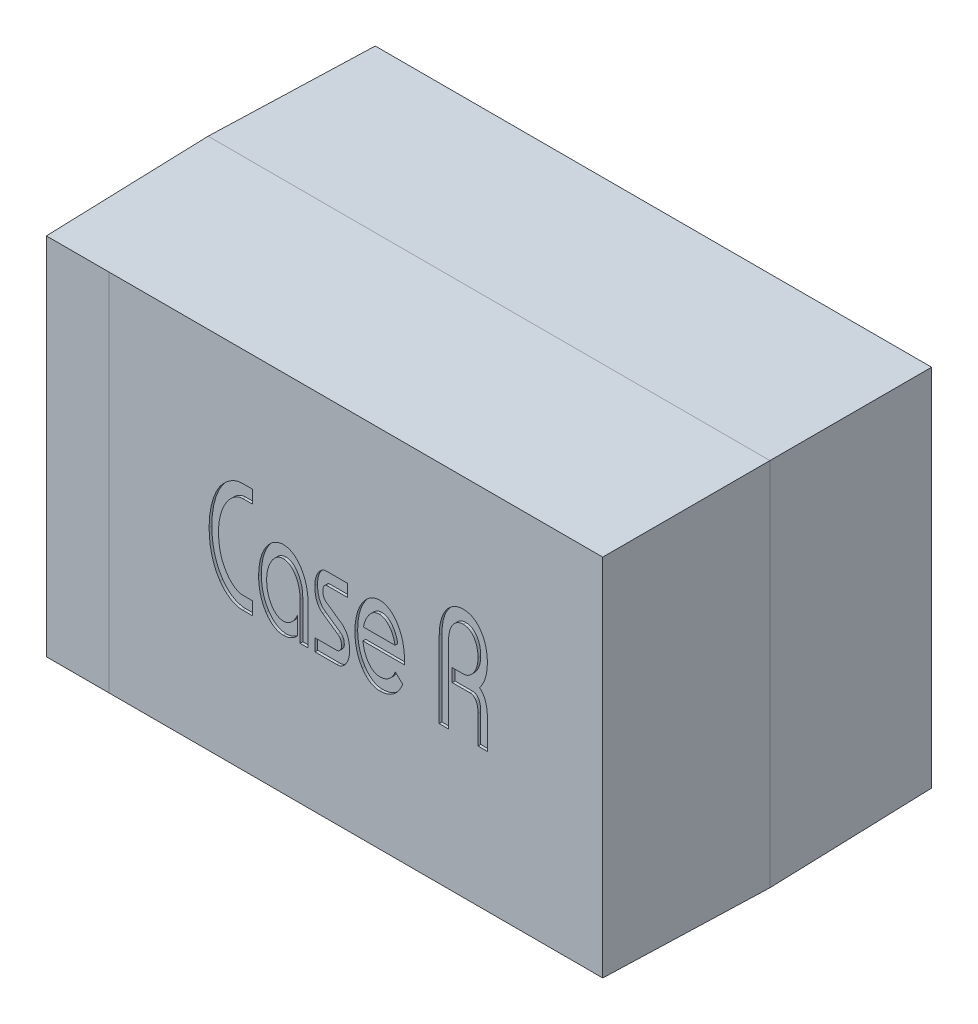
SolidWorks part; units mm, degrees
ref_plane "Front Plane" through (0, 0, 0) normal (0, 0, 1) x (1, 0, 0)
ref_plane "Top Plane" through (0, 0, 0) normal (0, 1, 0) x (1, 0, 0)
ref_plane "Right Plane" through (0, 0, 0) normal (1, 0, 0) x (0, 0, -1)
sketch "Sketch1" plane through (0, 0, 0) normal (0, 0, 1) x (1, 0, 0)
  line L1 (0, 0) -> (2.05, 0)
  line L2 (0, 0) -> (0, 1.35)
  line L3 (0, 1.35) -> (2.05, 1.35)
  line L4 (2.05, 0) -> (2.05, 1.35)
  dimension "D1" = 2.05
  dimension "D2" = 1.35
extrude "Boss-Extrude1" add sketch "Sketch1" along normal blind 1.2
chamfer "Chamfer3" distance 0.6 distance2 0.01 4 edges at (2.05, 0.675, 1.2) (1.025, 0, 1.2) (0, 0.675, 1.2) (1.025, 1.35, 1.2) first distance on face at (2.05, 0.675, 0.6) first distance on face at (1.025, 0, 0.6) first distance on face at (0, 0.675, 0.6) first distance on face at (1.025, 1.35, 0.6)
chamfer "Chamfer4" distance 0.01 distance2 0.6 4 edges at (1.025, 1.35, 0) (0, 0.675, 0) (1.025, 0, 0) (2.05, 0.675, 0) first distance on face at (1.025, 0.675, 0)
sketch "Sketch3" plane through (0, 0, 1.2) normal (0, 0, 1) x (1, 0, 0)
  line L0 (2.04, 1.34) -> (0.01, 1.34) construction
  line L1 (0.2384, 1.34) -> (0.01, 1.34)
  line L2 (0.2384, 1.34) -> (0.2384, 0.01)
  line L3 (0.2384, 0.01) -> (0.01, 0.01)
  line L4 (0.01, 1.34) -> (0.01, 0.01)
  line L5 (0.01, 0.01) -> (2.04, 0.01) construction
extrude "Cut-Extrude1" cut sketch "Sketch3" against normal blind 0.01
sketch "Sketch4" plane through (0, 0, 1.19) normal (0, 0, 1) x (1, 0, 0)
  line L1 (0.01, 1.34) -> (0.2384, 1.34)
  line L2 (0.01, 1.34) -> (0.01, 0.01)
  line L3 (0.01, 0.01) -> (0.2384, 0.01)
  line L4 (0.2384, 1.34) -> (0.2384, 0.01)
  line L6 (0.01, 0.01) -> (0.2384, 0.01) construction
extrude "Boss-Extrude4" add sketch "Sketch4" along normal blind 0.01 separate body
sketch "Sketch5" plane through (0, 0, 1.2) normal (0, 0, 1) x (1, 0, 0)
  text T0 "Case R" font "Belgium" height 0.4
extrude "Cut-Extrude2" cut sketch "Sketch5" against normal blind 0.01
